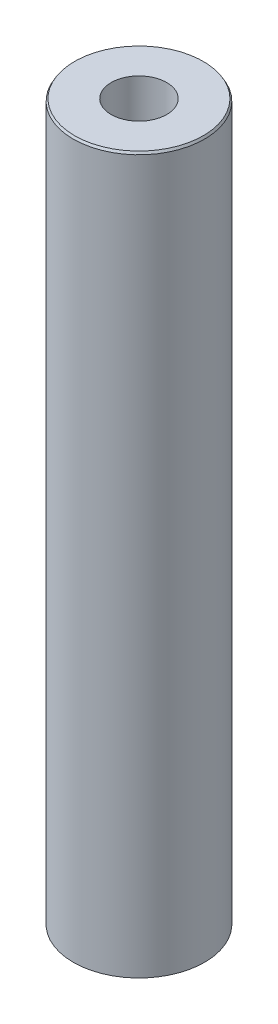
SolidWorks part; units mm, degrees
ref_plane "Front Plane" through (0, 0, 0) normal (0, 0, 1) x (1, 0, 0)
ref_plane "Top Plane" through (0, 0, 0) normal (0, 1, 0) x (1, 0, 0)
ref_plane "Right Plane" through (0, 0, 0) normal (1, 0, 0) x (0, 0, -1)
sketch "Sketch1" plane through (0, 0, 0) normal (0, 1, 0) x (1, 0, 0)
  circle A0 centre (0, 0) radius 55
  dimension "SHAFT_OD" = 110
extrude "Boss-Extrude1" add sketch "Sketch1" along normal blind 600
sketch "Sketch2" plane through (0, 0, 0) normal (0, 1, 0) x (1, 0, 0)
  circle A0 centre (0, 0) radius 23.2509
  dimension "BORE_D" = 46.5018
extrude "Cut-Extrude1" cut sketch "Sketch2" along normal through all
chamfer "Chamfer1" distance 1.9169 angle 30 2 edges at (0, 600, 55) (0, 0, 55) first distance on face at (0, 600, 55) first distance on face at (0, 0, 23.2509)
